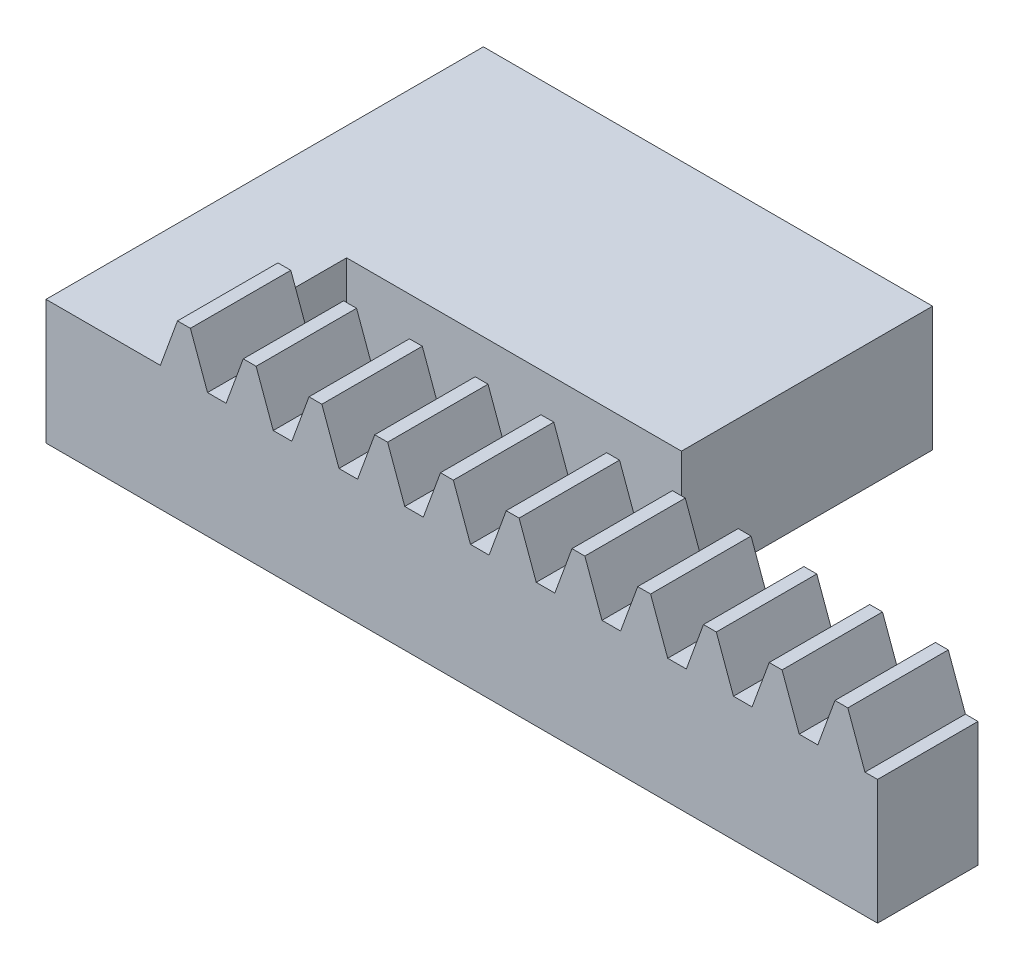
SolidWorks part; units mm, degrees
extrude "Blank" add sketch "BlankSke" against normal blind 5
sketch "BlankSke" plane through (0, 0, 0) normal (0, 0, 1) x (1, 0, 0)
  line L1 (0, 0) -> (53, 0)
  line L2 (0, 0) -> (0, 8.2)
  line L3 (0, 8.2) -> (53, 8.2)
  line L4 (53, 0) -> (53, 8.2)
  dimension "Length" = 53
ref_plane "Plane1" through (0, 0, 0) normal (0, 0, 1) x (1, 0, 0)
ref_plane "Plane2" through (0, 0, 0) normal (0, 1, 0) x (1, 0, 0)
ref_plane "Plane3" through (0, 0, 0) normal (1, 0, 0) x (0, 0, -1)
sketch "HoldingSke" plane through (0, 0, 0) normal (0, 1, 0) x (1, 0, 0)
  line L0 (0, 0) -> (0.1392, 0.9903)
  line L1 (-15, 0) -> (100, 0) construction
  line L2 (0, 0) -> (-2.1039, 2.3779)
  line L3 (0, 0) -> (-11.863, 4.5341)
  line L4 (0, 0) -> (8.2133, 2.6687)
  line L5 (0, 0) -> (-23.7986, -8.8762)
  line L6 (0, 0) -> (-10.5278, -7.1032)
  line L9 (-71.009, 38.7566) -> (-21.2053, 56.8837)
  line L10 (-76.2, 3.3779) -> (-69, 3.3779)
  line L11 (0, 0) -> (-5, 0)
  line L12 (-76.2, 101.6) -> (-76.162, 101.6)
  line L13 (24.9733, 27.94) -> (52.9518, 28.4284)
  line L14 (24.9733, 27.94) -> (24.9743, 27.94)
  line L15 (24.9733, 27.94) -> (100.4006, 29.5858)
  circle A0 centre (0, 0) radius 19.05
  circle A1 centre (0, 0) radius 3.6
  circle A2 centre (0, 0) radius 12.7
  dimension "Num_teeth" = 18
  dimension "Width" = 5
  dimension "Length" = 53
  dimension "Pitch_height" = 7.2
sketch "TooCutSkeIll" plane through (0, 0, 0) normal (0, 0, 1) x (1, 0, 0)
  line L0 (-1.2538, 8.1737) -> (-0.5045, 6.1152)
  line L1 (-0.2687, 5.95) -> (0.2687, 5.95)
  line L2 (0.5045, 6.1152) -> (1.2538, 8.1737)
  line L3 (53, 8.2) -> (0, 8.2) construction
  line L4 (0, 0) -> (0, 64.897) construction
  line L5 (-13.208, 7.2) -> (12.954, 7.2) construction
  line L6 (0, 0) -> (53, 0) construction
  line L7 (0.8994, 7.2) -> (0.8994, 48.7463) construction
  line L8 (-0.8994, 7.2) -> (-0.8994, 48.7463) construction
  line L9 (1.2914, 8.2) -> (1.2914, 8.2254)
  line L10 (-1.2914, 8.2) -> (-1.2914, 8.2254)
  line L11 (-1.2914, 8.2254) -> (1.2914, 8.2254)
  arc A0 (0.2687, 5.95) -> (0.5045, 6.1152) centre (0.2687, 6.201) ccw
  arc A1 (-0.5045, 6.1152) -> (-0.2687, 5.95) centre (-0.2687, 6.201) ccw
  arc A2 (1.2914, 8.2) -> (1.2538, 8.1737) centre (1.2914, 8.16) ccw
  arc A3 (-1.2538, 8.1737) -> (-1.2914, 8.2) centre (-1.2914, 8.16) ccw
  dimension "Addendum_plus" = 1.0254
  dimension "Pitch_height" = 7.2
  dimension "Pressure_angle" = 20
  dimension "Gap_width" = 1.7988
  dimension "Dedendum" = 1.25
extrude "ToothCutIll" [suppressed] cut sketch "TooCutSkeIll" against normal through all
sketch "TooCutSkeSim" plane through (0, 0, 0) normal (0, 0, 1) x (1, 0, 0)
  line L0 (0.4444, 5.95) -> (-0.4444, 5.95)
  line L1 (1.2726, 8.2254) -> (0.4444, 5.95)
  line L2 (0, 17.4625) -> (0, 53.467) construction
  line L3 (1.2726, 8.2254) -> (-1.2726, 8.2254)
  line L6 (-1.2726, 8.2254) -> (-0.4444, 5.95)
  line L9 (-0.8994, 7.2) -> (0.8994, 7.2) construction
  line L10 (0, 0) -> (53, 0) construction
  line L11 (0.8994, 7.2) -> (0.8994, 53.467) construction
  line L12 (-0.8994, 7.2) -> (-0.8994, 53.467) construction
  dimension "Addendum_plus" = 1.0254
  dimension "Pitch_height" = 7.2
  dimension "Pressure_angle" = 20
  dimension "Gap_width" = 1.7988
  dimension "Dedendum" = 1.25
extrude "ToothCutSim" cut sketch "TooCutSkeSim" against normal through all
pattern_linear "TeethCuts" count 18 spacing 3.1416 along (1, 0, 0) of "ToothCutIll", "ToothCutSim"
sketch "Sketch2" plane through (0, 0, -5) normal (0, 0, -1) x (-1, 0, 0)
  line L6 (-6.7276, 5.95) -> (0, 5.95)
  line L7 (-6.7276, 5.95) -> (-6.7276, 0)
  line L8 (-6.7276, 0) -> (0, 0)
  line L9 (0, 5.95) -> (0, 0)
extrude "Boss-Extrude1" add sketch "Sketch2" along normal blind 20
sketch "Sketch3" plane through (6.7276, 0, 0) normal (1, 0, 0) x (0, 0, -1)
  line L0 (25, 5.95) -> (5, 5.95) construction
  line L1 (9, 5.95) -> (21, 5.95)
  line L2 (9, 5.95) -> (9, 0)
  line L3 (9, 0) -> (21, 0)
  line L4 (21, 5.95) -> (21, 0)
  line L5 (25, 0) -> (5, 0) construction
  line L6 (5, 5.95) -> (5, 0) construction
  line L7 (25, 5.95) -> (25, 0) construction
  dimension "D1" = 4
  dimension "D2" = 4
extrude "Boss-Extrude2" add sketch "Sketch3" along normal blind 16
sketch "Sketch4" plane through (0, 0, -25) normal (0, 0, -1) x (-1, 0, 0)
  line L1 (-6.7276, 5.95) -> (0, 5.95)
  line L2 (-6.7276, 5.95) -> (-6.7276, 0)
  line L3 (-6.7276, 0) -> (0, 0)
  line L4 (0, 5.95) -> (0, 0)
extrude "Cut-Extrude1" cut sketch "Sketch4" against normal up to surface (4 mm away) up to face at (14.7276, 2.975, -21)
sketch "Sketch5" plane through (53, 0, 0) normal (1, 0, 0) x (0, 0, -1)
  line L1 (0, 0) -> (5, 0)
  line L2 (0, 0) -> (0, 5.95)
  line L3 (0, 5.95) -> (5, 5.95)
  line L4 (5, 0) -> (5, 5.95)
sketch "Sketch7" plane through (0, 0, -5) normal (0, 0, -1) x (-1, 0, 0)
  line L1 (-53, 0) -> (-40.998, 0)
  line L2 (-53, 0) -> (-53, 8.2)
  line L3 (-53, 8.2) -> (-40.998, 8.2)
  line L4 (-40.998, 0) -> (-40.998, 8.2)
  dimension "D1" = 12.002
extrude "Cut-Extrude3" cut sketch "Sketch7" against normal blind 9.55
sketch "Sketch9" plane through (0, 0, 0) normal (0, -1, 0) x (1, 0, 0)
  line L0 (22.7276, -21) -> (0, -21) construction
  line L1 (0, 0) -> (1.263, 0)
  line L2 (0, 0) -> (0, -21)
  line L3 (0, -21) -> (1.263, -21)
  line L4 (1.263, 0) -> (1.263, -21)
  dimension "D1" = 1.263
extrude "Cut-Extrude4" cut sketch "Sketch9" against normal blind 9.55
sketch "Sketch10" plane through (0, 0, 0) normal (0, 0, 1) x (1, 0, 0)
  line L0 (1.263, 8.199) -> (1.263, 0) construction
  line L5 (5.8387, 5.95) -> (1.263, 5.95)
  line L6 (5.8387, 5.95) -> (5.8387, 8.6767)
  line L7 (5.8387, 8.6767) -> (1.263, 8.6767)
  line L8 (1.263, 5.95) -> (1.263, 8.6767)
  dimension "D1" = 0
extrude "Cut-Extrude6" cut sketch "Sketch10" against normal blind 9.55
extrude "Cut-Extrude7" cut sketch "BlankSke<2>" against normal blind 0.1
sketch "BlankSke<2>" plane through (0, 0, 0) normal (0, 0, 1) x (1, 0, 0) same geometry as "BlankSke"
sketch "Sketch11" plane through (0, 0, -5) normal (0, 0, -1) x (-1, 0, 0)
  line L1 (-40.998, 0) -> (-6.7276, 0)
  line L2 (-40.998, 0) -> (-40.998, 11.8301)
  line L3 (-40.998, 11.8301) -> (-6.7276, 11.8301)
  line L4 (-6.7276, 0) -> (-6.7276, 11.8301)
extrude "Cut-Extrude8" cut sketch "Sketch11" against normal blind 0.1
equation "' \"Module@HoldingSke\" = 6.35"
equation "' \"Num_teeth@HoldingSke\" = 12"
equation "' \"Ap@HoldingSke\" =  20"
equation "' \"Ap@HoldingSke\" = 20"
equation "' \"Width@HoldingSke\" = 0.25 * 25.4"
equation "' \"Show_teeth@HoldingSke\" = 500"
equation "' \"Backlash@HoldingSke\" = 0.009 * 25.4"
equation "' \"Addendum_fac@HoldingSke\" = 1.0"
equation "' \"Dedendum_fac@HoldingSke\" = 1.25"
equation "' \"Dedendum_add@HoldingSke\" = 0.00005 * 25.4"
equation "' \"Clearance_fac@HoldingSke\" = 0.25"
equation "' \"Pitch_height@HoldingSke\" = 1 * 25.4"
equation "' \"Length@HoldingSke\" = 4.71 * 25.4"
equation "\"Pitch@HoldingSke\" = 1 / \"Module@HoldingSke\""
equation "\"MPH@HoldingSke\" = \"Dedendum_fac@HoldingSke\" / \"Pitch@HoldingSke\" + 2 * \"Dedendum_add@HoldingSke\" + 0.002 * 25.4"
equation "\"MPH@HoldingSke\" = ((sgn( \"MPH@HoldingSke\" - \"Pitch_height@HoldingSke\")+1)*( \"MPH@HoldingSke\" - \"Pitch_height@HoldingSke\"))/2 + \"Pitch_height@HoldingSke\""
equation "\"Blank_height@BlankSke\" = \"Pitch_height@HoldingSke\" + \"Addendum_fac@HoldingSke\"  / \"Pitch@HoldingSke\" "
equation "\"Length@BlankSke\" =  \"Length@HoldingSke\""
equation "\"Face_width@Blank\" = \"Width@HoldingSke\""
equation "\"Pressure_angle@TooCutSkeIll\" = \"Ap@HoldingSke\""
equation "\"Addendum_plus@TooCutSkeIll\" =  \"Addendum_fac@HoldingSke\"  / \"Pitch@HoldingSke\" + 0.001 *25.4"
equation "\"Dedendum@TooCutSkeIll\" = \"Dedendum_fac@HoldingSke\"  / \"Pitch@HoldingSke\""
equation "\"Pitch_height@TooCutSkeIll\" =  \"MPH@HoldingSke\""
equation "\"Gap_width@TooCutSkeIll\" = 3.14159265 / 2 / \"Pitch@HoldingSke\" + 6 * \"Backlash@HoldingSke\""
equation "\"Pressure_angle@TooCutSkeSim\" = \"Ap@HoldingSke\""
equation "\"Addendum_plus@TooCutSkeSim\" =  \"Addendum_fac@HoldingSke\"  / \"Pitch@HoldingSke\" + 0.001 * 25.4"
equation "\"Dedendum@TooCutSkeSim\" = \"Dedendum_fac@HoldingSke\"  / \"Pitch@HoldingSke\""
equation "\"Pitch_height@TooCutSkeSim\" =  \"MPH@HoldingSke\""
equation "\"Gap_width@TooCutSkeSim\" = 3.14159265 / 2 / \"Pitch@HoldingSke\" + 6 * \"Backlash@HoldingSke\""
equation "\"Root_fillet@TooCutSkeIll\" = \"Clearance_fac@HoldingSke\" / \"Pitch@HoldingSke\" + \"Dedendum_add@HoldingSke\""
equation "\"Break_rad@TooCutSkeIll\" = 0.02 / \"Pitch@HoldingSke\" * 2"
equation "\"Linear_pitch@TeethCuts\" = 3.14159265 / \"Pitch@HoldingSke\""
equation "\"Num_teeth@HoldingSke\" = int( ( \"Length@HoldingSke\" + 0 ) / (3.14159265 / \"Pitch@HoldingSke\")) + 0.9999  + 1"
equation " \"Num_teeth@TeethCuts\" = int( \"Show_teeth@HoldingSke\" ) + 1"
equation " \"Num_teeth@TeethCuts\" = ((sgn( \"Num_teeth@TeethCuts\" - \"Num_teeth@HoldingSke\" )-1)*( \"Num_teeth@TeethCuts\" - \"Num_teeth@HoldingSke\" ))/-2+ \"Num_teeth@HoldingSke\""
equation " \"Num_teeth@TeethCuts\" = ((sgn( \"Num_teeth@TeethCuts\" - 2.0)+1)*( \"Num_teeth@TeethCuts\" - 2.0))/2 +2.0"
